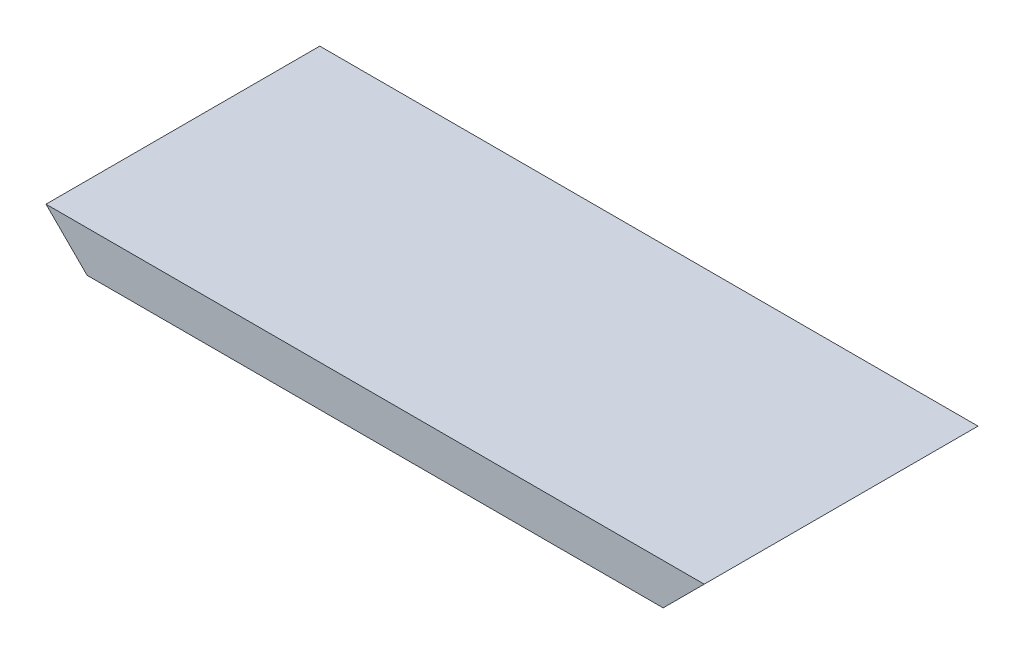
SolidWorks part; units mm, degrees
ref_plane "Front Plane" through (0, 0, 0) normal (0, 0, 1) x (1, 0, 0)
ref_plane "Top Plane" through (0, 0, 0) normal (0, 1, 0) x (1, 0, 0)
ref_plane "Right Plane" through (0, 0, 0) normal (1, 0, 0) x (0, 0, -1)
sketch "Sketch2" plane through (0, 0, 0) normal (0, 0, 1) x (1, 0, 0)
  line L0 (19, 0) -> (-19, 0) construction
  line L1 (-19, 0) -> (-22, 3) construction
  line L2 (-22, 3) -> (22, 3) construction
  line L3 (22, 3) -> (19, 0) construction
  line L4 (21.6379, 2.85) -> (18.9379, 0.15)
  line L5 (18.9379, 0.15) -> (-18.9379, 0.15)
  line L6 (-18.9379, 0.15) -> (-21.6379, 2.85)
  line L7 (-21.6379, 2.85) -> (21.6379, 2.85)
  point P4 (0, 0)
  dimension "D1" = 45
  dimension "D2" = 45
  dimension "D3" = 44
  dimension "D4" = 3
  dimension "D5" = 0.15
extrude "Boss-Extrude1" add sketch "Sketch2" against normal blind 18
sketch "Sketch4" plane through (0, 0.15, 0) normal (0, -1, 0) x (1, 0, 0)
  line L0 (-18.9379, 0) -> (18.9379, 0) construction
  line L1 (6, -11) -> (-6, -11)
  line L2 (6, -11) -> (6, -3)
  line L3 (6, -3) -> (-6, -3)
  line L4 (-6, -11) -> (-6, -3)
  line L5 (6, -11) -> (-6, -3) construction
  line L6 (6, -3) -> (-6, -11) construction
  point P0 (0, -7)
  point P7 (0, 0)
  dimension "D1" = 3
  dimension "D2" = 8
  dimension "D3" = 12
extrude "Cut-Extrude1" cut sketch "Sketch4" against normal blind 2
fillet "Fillet1" radius 10 1 edges at (0, 2.15, -11)
fillet "Fillet2" radius 0.5 1 edges at (0, 2.15, -3)
